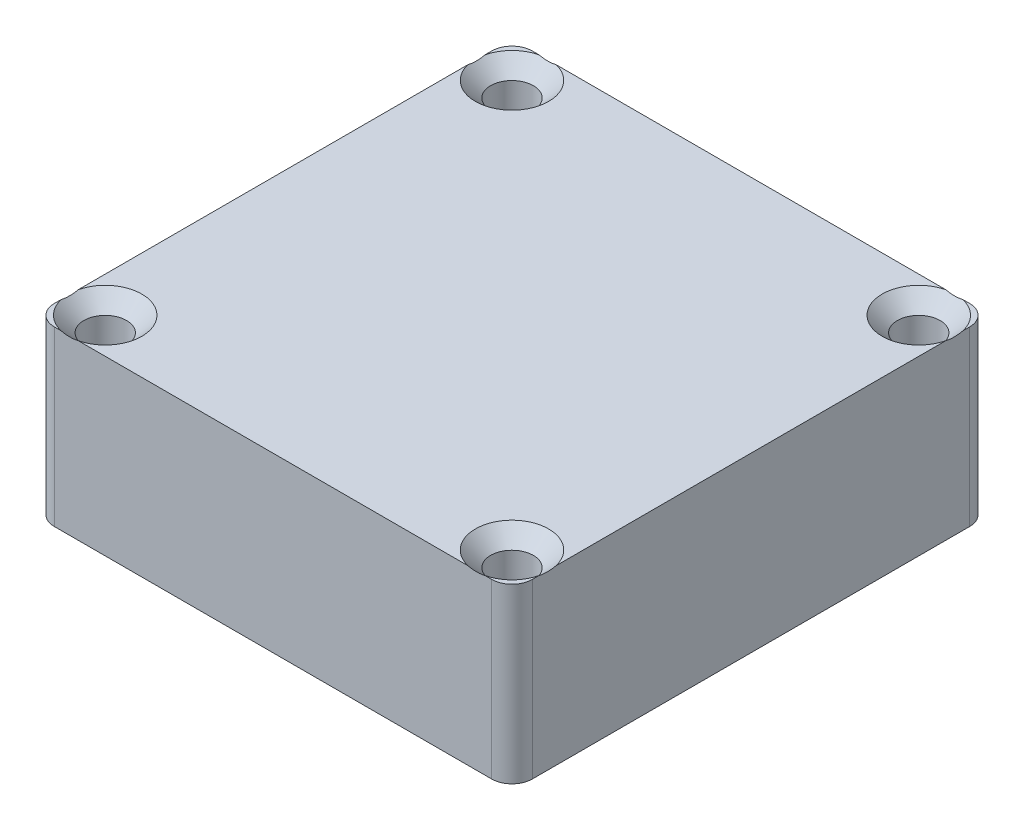
SolidWorks part; units mm, degrees
ref_plane "Спереди" through (0, 0, 0) normal (0, 0, 1) x (1, 0, 0)
ref_plane "Сверху" through (0, 0, 0) normal (0, 1, 0) x (1, 0, 0)
ref_plane "Справа" through (0, 0, 0) normal (1, 0, 0) x (0, 0, -1)
sketch "Эскиз1" plane through (0, 0, 0) normal (0, 1, 0) x (1, 0, 0)
  line L1 (0, 0) -> (-47, 0)
  line L2 (0, 0) -> (0, 47)
  line L3 (0, 47) -> (-47, 47)
  line L4 (-47, 0) -> (-47, 47)
  dimension "D1" = 47
  dimension "D2" = 47
extrude "Бобышка-Вытянуть1" add sketch "Эскиз1" along normal blind 17
sketch "Эскиз2" plane through (0, 0, 0) normal (0, -1, 0) x (1, 0, 0)
  line L0 (-47, 0) -> (0, 0) construction
  line L1 (-47, -47) -> (-47, 0) construction
  line L2 (-47, -23.5) -> (0, -23.5) construction
  line L3 (0, 0) -> (0, -47) construction
  line L4 (-23.5, -47) -> (-23.5, 0) construction
  line L5 (0, -47) -> (-47, -47) construction
  circle A0 centre (-43.5, -3.5) radius 2.1
  circle A1 centre (-3.5, -3.5) radius 2.1
  circle A2 centre (-3.5, -43.5) radius 2.1
  circle A3 centre (-43.5, -43.5) radius 2.1
  dimension "D1" = 4.2
  dimension "D2" = 3.5
  dimension "D3" = 3.5
extrude "Вырез-Вытянуть1" cut sketch "Эскиз2" against normal through all
sketch "Эскиз3" plane through (0, 0, 0) normal (0, -1, 0) x (1, 0, 0)
  line L0 (-47, -47) -> (-47, 0) construction
  line L1 (-40.8, -6.2) -> (-6.2, -6.2)
  line L2 (-40.8, -6.2) -> (-40.8, -40.8)
  line L3 (-40.8, -40.8) -> (-6.2, -40.8)
  line L4 (-6.2, -6.2) -> (-6.2, -40.8)
  line L5 (0, 0) -> (0, -47) construction
  line L6 (-47, 0) -> (0, 0) construction
  line L7 (0, -47) -> (-47, -47) construction
  dimension "D1" = 6.2
  dimension "D2" = 6.2
  dimension "D3" = 6.2
  dimension "D4" = 6.2
extrude "Вырез-Вытянуть2" cut sketch "Эскиз3" against normal blind 14.25
fillet "Скругление1" radius 2 4 edges at (0, 8.5, -47) (-47, 8.5, -47) (-47, 8.5, 0) (0, 8.5, 0)
fillet "Скругление2" radius 1.5 4 edges at (-6.2, 14.25, -23.5) (-23.5, 14.25, -6.2) (-23.5, 14.25, -40.8) (-40.8, 14.25, -23.5)
chamfer "Фаска1" distance 1.5 angle 45 4 edges at (-43.5, 17, -41.4) (-3.5, 17, -45.6) (-43.5, 17, -5.6) (-3.5, 17, -1.4)
fillet "Скругление3" radius 1.5 8 edges at (-6.6393, 13.8107, -40.3607) (-40.3607, 13.8107, -40.3607) (-6.6393, 13.8107, -6.6393) (-40.3607, 13.8107, -6.6393) (-6.2, 6.375, -40.8) (-40.8, 6.375, -40.8) (-6.2, 6.375, -6.2) (-40.8, 6.375, -6.2)
